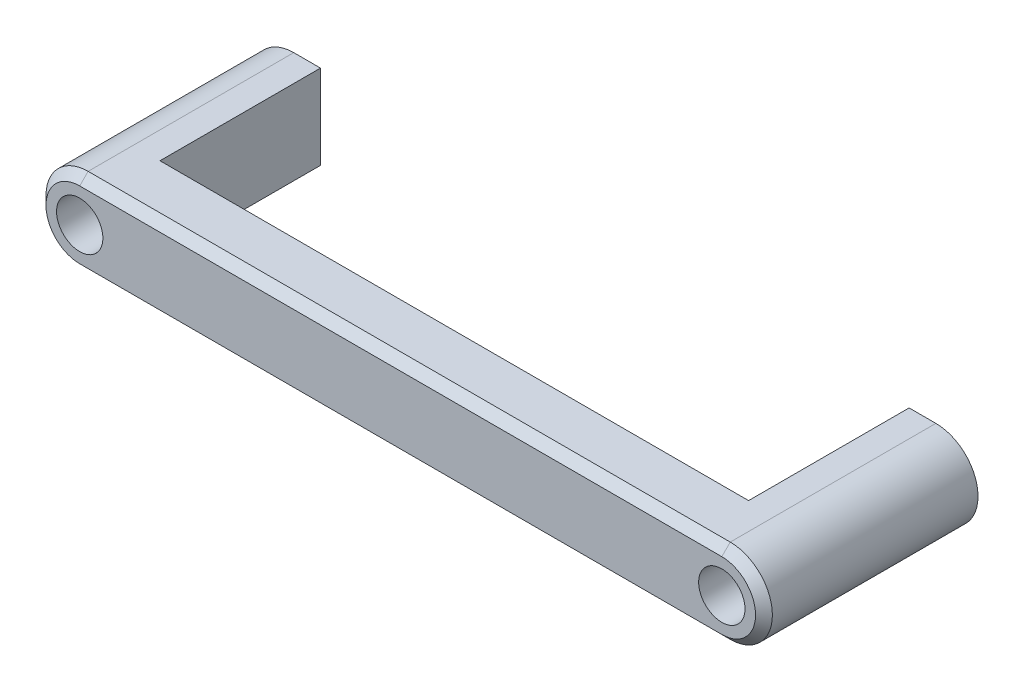
SolidWorks part; units mm, degrees
ref_plane "Front Plane" through (0, 0, 0) normal (0, 0, 1) x (1, 0, 0)
ref_plane "Top Plane" through (0, 0, 0) normal (0, 1, 0) x (1, 0, 0)
ref_plane "Right Plane" through (0, 0, 0) normal (1, 0, 0) x (0, 0, -1)
sketch "Sketch1" plane through (0, 0, 0) normal (0, 0, 1) x (1, 0, 0)
  line L0 (-76.2, 0) -> (76.2, 0) construction
  line L1 (-76.2, 10) -> (76.2, 10)
  line L2 (-76.2, -10) -> (76.2, -10)
  arc A0 (-76.2, 10) -> (-76.2, -10) centre (-76.2, 0) ccw
  arc A1 (76.2, -10) -> (76.2, 10) centre (76.2, 0) ccw
  point P2 (0, 0)
  dimension "D1" = 152.4
  dimension "D2" = 20
extrude "Boss-Extrude1" add sketch "Sketch1" along normal blind 50.8
sketch "Sketch2" plane through (0, 0, 50.8) normal (0, 0, 1) x (1, 0, 0)
  circle A0 centre (-76.2, 0) radius 3.75
  circle A1 centre (76.2, 0) radius 3.75
  dimension "D1" = 7.5
extrude "Cut-Extrude1" cut sketch "Sketch2" against normal blind 50.8
sketch "Sketch3" plane through (0, 10, 0) normal (0, 1, 0) x (1, 0, 0)
  line L0 (76.2, 0) -> (-76.2, 0) construction
  line L1 (-69.85, 0) -> (69.85, 0)
  line L2 (-69.85, 0) -> (-69.85, -38.1)
  line L3 (-69.85, -38.1) -> (69.85, -38.1)
  line L4 (69.85, 0) -> (69.85, -38.1)
  point P6 (0, 0)
  point P7 (0, 0)
  dimension "D1" = 139.7
  dimension "D2" = 38.1
extrude "Cut-Extrude2" cut sketch "Sketch3" against normal blind 50.8
sketch "Sketch4" plane through (0, 0, 50.8) normal (0, 0, 1) x (1, 0, 0)
  circle A0 centre (-76.2, 0) radius 5.5
  circle A1 centre (76.2, 0) radius 5.5
  dimension "D1" = 11
extrude "Cut-Extrude3" cut sketch "Sketch4" against normal blind 35
chamfer "Chamfer1" distance 2 angle 45 4 edges at (0, -10, 50.8) (86.2, 0, 50.8) (-86.2, 0, 50.8) (0, 10, 50.8)
chamfer "Chamfer2" distance 2 angle 45 2 edges at (79.95, 0, 15.8) (-72.45, 0, 15.8)
